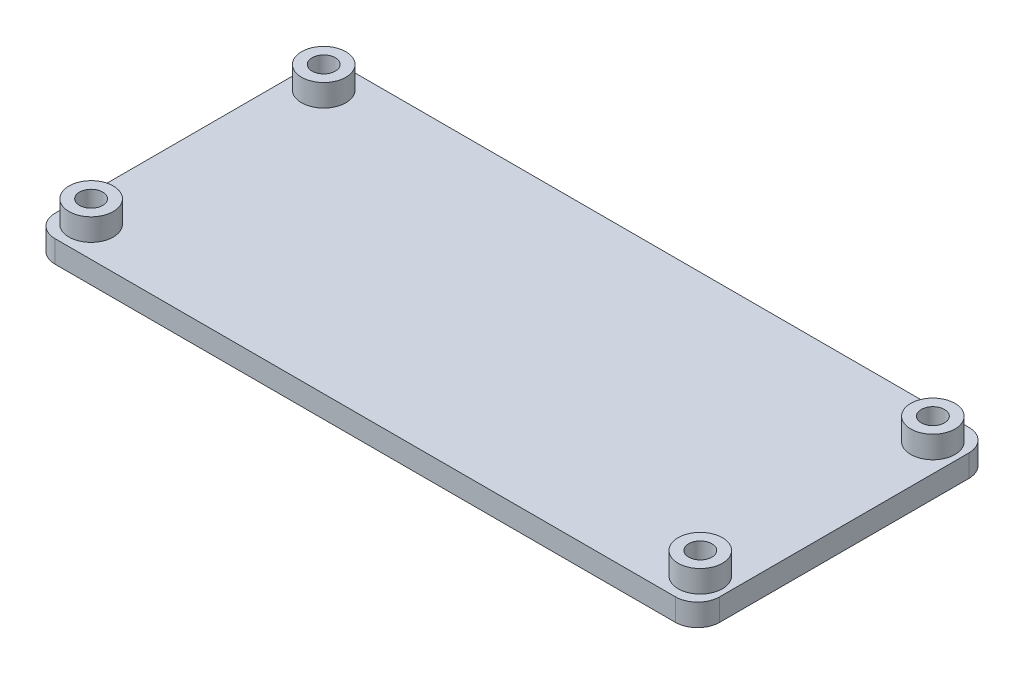
SolidWorks part; units mm, degrees
ref_plane "Front Plane" through (0, 0, 0) normal (0, 0, 1) x (1, 0, 0)
ref_plane "Top Plane" through (0, 0, 0) normal (0, 1, 0) x (1, 0, 0)
ref_plane "Right Plane" through (0, 0, 0) normal (1, 0, 0) x (0, 0, -1)
sketch "Sketch1" plane through (0, 0, 0) normal (0, 1, 0) x (1, 0, 0)
  line L1 (-30, 13.25) -> (30, 13.25)
  line L2 (-30, 13.25) -> (-30, -13.25)
  line L3 (-30, -13.25) -> (30, -13.25)
  line L4 (30, 13.25) -> (30, -13.25)
  dimension "D1" = 60
  dimension "D2" = 26.5
  dimension "D3" = 13.25
  dimension "D4" = 30
extrude "Boss-Extrude1" add sketch "Sketch1" along normal blind 2
sketch "Sketch2" plane through (0, 2, 0) normal (0, 1, 0) x (1, 0, 0)
  circle A0 centre (-27.5, 10.5) radius 2
  circle A1 centre (27.5, 10.5) radius 2
  circle A2 centre (27.5, -10.5) radius 2
  circle A3 centre (-27.5, -10.5) radius 2
  dimension "D1" = 4
  dimension "D2" = 4
  dimension "D3" = 4
  dimension "D4" = 4
  dimension "D5" = 55
  dimension "D6" = 21
  dimension "D7" = 55
  dimension "D8" = 21
  dimension "D9" = 27.5
  dimension "D10" = 10.5
fillet "Fillet1" radius 2 4 edges at (-30, 1, -13.25) (30, 1, -13.25) (30, 1, 13.25) (-30, 1, 13.25)
extrude "Boss-Extrude2" add sketch "Sketch2" along normal blind 2
sketch "Sketch4" plane through (0, 4, 0) normal (0, 1, 0) x (1, 0, 0)
  circle A0 centre (-27.5, 10.5) radius 1.05
  circle A1 centre (-27.5, -10.5) radius 1.05
  circle A2 centre (27.5, -10.5) radius 1.05
  circle A3 centre (27.5, 10.5) radius 1.05
  dimension "D1" = 2.1
  dimension "D2" = 2.1
  dimension "D3" = 2.1
  dimension "D4" = 2.1
extrude "Cut-Extrude2" cut sketch "Sketch4" against normal blind 12
